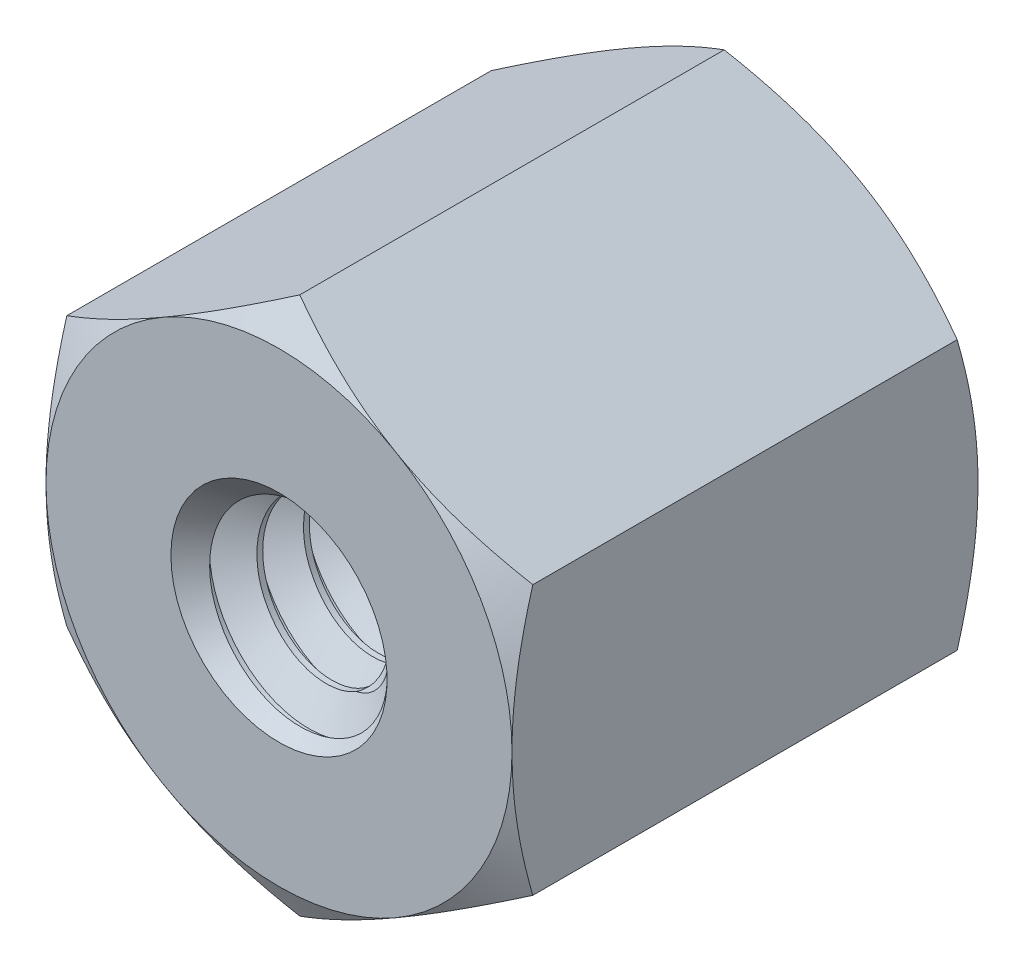
SolidWorks part; units mm, degrees
material "6061-T6 (SS)"
ref_plane "Front Plane" through (0, 0, 0) normal (0, 0, 1) x (1, 0, 0)
ref_plane "Top Plane" through (0, 0, 0) normal (0, 1, 0) x (1, 0, 0)
ref_plane "Right Plane" through (0, 0, 0) normal (1, 0, 0) x (0, 0, -1)
sketch "Sketch3" plane through (0, 0, 0) normal (1, 0, 0) x (0, 0, -1)
  line L0 (-3.175, 0) -> (3.175, 0) construction
  line L1 (0, 3.175) -> (0, -3.175) construction
  line L2 (-3.175, 1.4224) -> (-3.175, -1.4224) construction
  point P2 (-1.5875, 0)
  point P3 (1.5875, 0)
  dimension "D1" = 4.7625
  dimension "Length" = 6.35
  dimension "Min Thread Length" = 4.7625
  dimension "Thread Dia" = 2.8448
  dimension "Hex" = 6.35
sketch "Sketch1" plane through (0, 0, 0) normal (0, 0, 1) x (1, 0, 0)
  line L1 (0, 3.6662) -> (-3.175, 1.8331)
  line L2 (-3.175, 1.8331) -> (-3.175, -1.8331)
  line L3 (-3.175, -1.8331) -> (0, -3.6662)
  line L4 (0, -3.6662) -> (3.175, -1.8331)
  line L5 (3.175, -1.8331) -> (3.175, 1.8331)
  line L6 (3.175, 1.8331) -> (0, 3.6662)
  circle A0 centre (0, 0) radius 3.175 construction
  circle A1 centre (0, 0) radius 1.4224
extrude "Extrude1" add sketch "Sketch1" along normal up to vertex (3.175 mm away) and the other way up to vertex (3.175 mm away) up to point (0, 0, 3.175) other way up to point (0, 0, -3.175)
sketch "Sketch11" plane through (0, 0, -3.175) normal (0, 0, -1) x (-1, 0, 0)
  circle A0 centre (0, 0) radius 1.4224 construction
  circle A1 centre (0, 0) radius 1.4224
curve "Helix/Spiral1" pitch 0.635 height 6.985 radius 1.4224 centre (0, 0, -3.175) axis (0, 0, 1) start towards (0, 1, 0) parameters "Pitch"=0.635
sketch "Sketch12" plane through (0, 0, 0) normal (1, 0, 0) x (0, 0, -1)
  line L0 (3.7306, 1.4224) -> (3.175, 1.4224)
  line L1 (3.7306, 1.4224) -> (3.4925, 1.01)
  line L2 (3.4925, 1.01) -> (3.4131, 1.01)
  line L3 (3.4131, 1.01) -> (3.175, 1.4224)
  line L4 (3.4528, 1.01) -> (3.4528, 1.4224) construction
  line L5 (3.6116, 1.2162) -> (3.2941, 1.2162) construction
  dimension "D1" = 0.0794
  dimension "D2" = 0.3175
  dimension "D3" = 60
sweep "Sweep1" add profiles "Sketch12" path "Helix/Spiral1"
sketch "Sketch6" plane through (0, 0, -3.175) normal (0, 0, -1) x (-1, 0, 0)
  line L6 (0, 3.6662) -> (-3.175, 1.8331)
  line L7 (-3.175, 1.8331) -> (-3.175, -1.8331)
  line L8 (-3.175, -1.8331) -> (0, -3.6662)
  line L9 (0, -3.6662) -> (3.175, -1.8331)
  line L10 (3.175, -1.8331) -> (3.175, 1.8331)
  line L11 (3.175, 1.8331) -> (0, 3.6662)
  line L12 (0, 3.6662) -> (-3.175, 1.8331)
  line L13 (-3.175, 1.8331) -> (-3.175, -1.8331)
  line L14 (-3.175, -1.8331) -> (0, -3.6662)
  line L15 (0, -3.6662) -> (3.175, -1.8331)
  line L16 (3.175, -1.8331) -> (3.175, 1.8331)
  line L17 (3.175, 1.8331) -> (0, 3.6662)
  dimension "D1" = 0
extrude "Extrude2" cut sketch "Sketch6" along normal through all
sketch "Sketch7" plane through (0, 0, -3.175) normal (0, 0, -1) x (-1, 0, 0)
  circle A2 centre (0, 0) radius 1.4732
  circle A3 centre (0, 0) radius 1.4732
  dimension "D1" = 0.0508
extrude "Extrude3" cut sketch "Sketch7" against normal through all draft 43
sketch "Sketch8" plane through (0, 0, -3.175) normal (0, 0, -1) x (-1, 0, 0)
  circle A0 centre (0, 0) radius 3.175 construction
  circle A1 centre (0, 0) radius 3.175
extrude "Extrude4" cut sketch "Sketch8" against normal through all draft 60 flip side to cut
mirror "Mirror1" about plane through (0, 0, 0) normal (0, 0, 1) of "Extrude2", "Extrude3", "Extrude4"
sketch "Sketch9" [suppressed] plane through (0, 0, 0) normal (1, 0, 0) x (0, 0, -1)
  line L1 (-1.5875, 0.8128) -> (1.5875, 0.8128)
  line L2 (-1.5875, 0.8128) -> (-1.5875, 0)
  line L3 (-1.5875, 0) -> (1.5875, 0)
  line L4 (1.5875, 0.8128) -> (1.5875, 0)
  line L7 (-6.35, 0) -> (6.35, 0) construction
revolve "Revolve" [suppressed] add sketch "Sketch9" angle 360 about L0
sketch "Sketch10" [suppressed] plane through (0, 0, 0) normal (1, 0, 0) x (0, 0, -1)
  line L0 (6.35, 0.762) -> (1.5875, 0.762)
  line L1 (-6.35, 0.762) -> (-1.5875, 0.762)
  line L2 (1.5875, 0.762) -> (1.5875, -0.762)
  line L3 (-6.35, -0.8128) -> (-1.5875, -0.8128)
  line L4 (-1.5875, 0.762) -> (-1.5875, -0.8128)
  line L5 (1.5875, -0.762) -> (6.35, -0.762)
equation "\"D1@Sketch3\" = \"Min Thread Length@Sketch3\""
equation "\"D3@Helix/Spiral1\" = \"Length@Sketch3\"+\"Pitch@Helix/Spiral1\""
equation "\"D1@Sketch12\" = \"Pitch@Helix/Spiral1\"*.125"
equation "\"D2@Sketch12\" = \"Pitch@Helix/Spiral1\"*.5"
